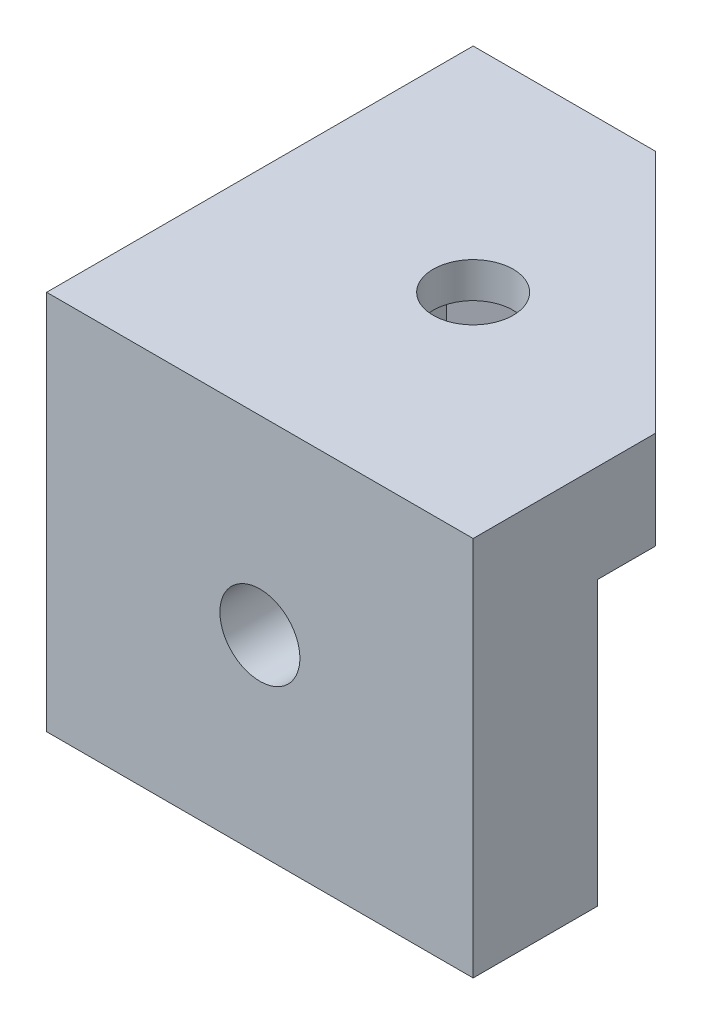
SolidWorks part; units mm, degrees
ref_plane "Front Plane" through (0, 0, 0) normal (0, 0, 1) x (1, 0, 0)
ref_plane "Top Plane" through (0, 0, 0) normal (0, 1, 0) x (1, 0, 0)
ref_plane "Right Plane" through (0, 0, 0) normal (1, 0, 0) x (0, 0, -1)
sketch "Sketch1" plane through (0, 0, 0) normal (0, 1, 0) x (1, 0, 0)
  line L1 (0, 0) -> (38.1, 0)
  line L5 (0, 0) -> (0, 38.1)
  line L6 (0, 38.1) -> (38.1, 38.1)
  line L8 (38.1, 38.1) -> (38.1, 0)
  dimension "D1" = 38.1
extrude "Main Body" add sketch "Sketch1" along normal blind 34
sketch "Sketch3" plane through (0, 0, 0) normal (0, 0, 1) x (1, 0, 0)
  line L0 (0, 0) -> (38.1, 34) construction
  circle A0 centre (19.05, 17) radius 3.5719
  circle A1 centre (19.05, 17) radius 7.9375 construction
  dimension "D1" = 7.1437
  dimension "D2" = 15.875
extrude "9/32 Right Rail" cut sketch "Sketch3" against normal blind 5.5562 and the other way through all
sketch "Sketch4" plane through (0, 0, 0) normal (-1, 0, 0) x (0, 0, 1)
  line L0 (0, 0) -> (-38.1, 34) construction
  circle A0 centre (-19.05, 17) radius 3.5719
  circle A1 centre (-19.05, 17) radius 7.9375 construction
  dimension "D1" = 7.1437
  dimension "D2" = 15.875
extrude "9/32 Left Rail" cut sketch "Sketch4" against normal blind 5.5562
sketch "Sketch8" plane through (0, 34, 0) normal (0, 1, 0) x (1, 0, 0)
  line L0 (0, 0) -> (38.1, 38.1) construction
  circle A0 centre (19.05, 19.05) radius 3.175 construction
  circle A1 centre (19.05, 19.05) radius 7.9375 construction
  circle A2 centre (19.05, 19.05) radius 3.5719
  dimension "D1" = 6.35
  dimension "D2" = 15.875
  dimension "D3" = 0.3969
extrude "9/32 Topper" cut sketch "Sketch8" against normal blind 10 and the other way through all
ref_plane "Plane1" through (5.5562, 0, 0) normal (-1, 0, 0) x (0, 0, 1)
sketch "Sketch9" plane through (0, 0, 0) normal (-1, 0, 0) x (0, 0, 1)
  line L0 (-19.05, 0) -> (-19.05, 34) construction
  line L1 (-12.6342, 17) -> (-15.8421, 22.5562) construction
  line L2 (-15.8421, 22.5562) -> (-22.2579, 22.5562) construction
  line L3 (-22.2579, 22.5562) -> (-25.4658, 17) construction
  line L4 (-25.4658, 17) -> (-22.2579, 11.4437) construction
  line L5 (-22.2579, 11.4437) -> (-15.8421, 11.4437) construction
  line L6 (-15.8421, 11.4437) -> (-12.6342, 17) construction
  line L7 (-38.1, 0) -> (0, 0) construction
  line L8 (-38.1, 34) -> (0, 34) construction
  line L9 (-22.3152, 22.6555) -> (-25.5804, 17)
  line L10 (-25.5804, 17) -> (-22.3152, 11.3445)
  line L11 (-22.3152, 11.3445) -> (-15.7848, 11.3445)
  line L12 (-15.7848, 11.3445) -> (-12.5196, 17)
  line L13 (-12.5196, 17) -> (-15.7848, 22.6555)
  line L14 (-15.7848, 22.6555) -> (-22.3152, 22.6555)
  line L15 (-38.1, 27.65) -> (-38.1, 6.35) construction
  line L16 (-38.1, 34) -> (-38.1, 0) construction
  line L17 (-38.1, 6.35) -> (-5.5562, 6.35) construction
  line L18 (-5.5562, 6.35) -> (-5.5562, 27.65) construction
  line L19 (-5.5562, 27.65) -> (-38.1, 27.65) construction
  line L20 (0, 34) -> (0, 0) construction
  circle A0 centre (-19.05, 17) radius 5.5563 construction
  point P15 (-19.05, 17)
  point P27 (-38.1, 17)
  point P29 (-38.1, 17)
  dimension "D1" = 11.1125
  dimension "D3" = 5.5562
  dimension "D4" = 6.35
  dimension "D2" = 0.0992
extrude "Hex Hole Right" cut sketch "Sketch9" against normal up to surface (38.1 mm away) from surface up to face at (38.1, 17, -19.05) starting at plane "Plane1"
ref_plane "Plane2" through (0, 0, -5.5563) normal (0, 0, 1) x (1, 0, 0)
sketch "Sketch10" plane through (0, 0, 0) normal (0, 0, 1) x (1, 0, 0)
  line L0 (19.05, 0) -> (19.05, 34) construction
  line L1 (0, 0) -> (38.1, 0) construction
  line L2 (0, 34) -> (38.1, 34) construction
  line L3 (15.7848, 22.6555) -> (12.5196, 17)
  line L4 (25.4658, 17) -> (22.2579, 22.5562) construction
  line L5 (22.2579, 22.5562) -> (15.8421, 22.5562) construction
  line L6 (15.8421, 22.5562) -> (12.6342, 17) construction
  line L13 (12.6342, 17) -> (15.8421, 11.4437) construction
  line L14 (15.8421, 11.4437) -> (22.2579, 11.4437) construction
  line L15 (22.2579, 11.4437) -> (25.4658, 17) construction
  line L16 (12.5196, 17) -> (15.7848, 11.3445)
  line L17 (15.7848, 11.3445) -> (22.3152, 11.3445)
  line L18 (22.3152, 11.3445) -> (25.5804, 17)
  line L19 (25.5804, 17) -> (22.3152, 22.6555)
  line L20 (22.3152, 22.6555) -> (15.7848, 22.6555)
  circle A0 centre (19.05, 17) radius 5.5563 construction
  dimension "D1" = 11.1125
  dimension "D2" = 0.0992
extrude "Hex Hole Left" cut sketch "Sketch10" against normal up to surface (38.1 mm away) from surface up to face at (19.05, 17, -38.1) starting at plane "Plane2"
sketch "Sketch13" plane through (0, 34, 0) normal (0, 1, 0) x (1, 0, 0)
  line L0 (22.3152, 5.5563) -> (15.7848, 5.5563) construction
  line L1 (5.5562, 15.7848) -> (5.5562, 22.3152) construction
  line L2 (38.1, 11.1125) -> (11.1125, 11.1125)
  line L3 (11.1125, 38.1) -> (11.1125, 11.1125)
  line L5 (22.3152, 5.5563) -> (15.7848, 5.5563) construction
  line L6 (5.5562, 15.7848) -> (5.5562, 22.3152) construction
  line L7 (38.1, 38.1) -> (0, 38.1) construction
  line L8 (38.1, 0) -> (38.1, 38.1) construction
  line L9 (11.1125, 38.1) -> (38.1, 38.1)
  line L10 (38.1, 38.1) -> (38.1, 11.1125)
  dimension "D1" = 5.5562
ref_plane "Plane4" through (0, 17, 0) normal (0, 1, 0) x (1, 0, 0)
extrude "Inner Cavity" cut sketch "Sketch13" along direction (0, -1, 0) on the side of the normal offset from surface 8.7312 and the other way up to surface (34 mm away) from surface up to face at (19.05, 34, -22.6219) other way up to face at (19.05, 0, -19.05) starting at plane "Plane4"
sketch "Sketch14" plane through (0, 34, 0) normal (0, 1, 0) x (1, 0, 0)
  line L0 (38.1, 0) -> (0, 38.1) construction
  line L1 (24.7055, 22.3152) -> (19.05, 25.5804)
  line L2 (24.6063, 22.2579) -> (19.05, 25.4658) construction
  line L3 (19.05, 25.4658) -> (13.4938, 22.2579) construction
  line L4 (13.4938, 22.2579) -> (13.4938, 15.8421) construction
  line L5 (13.4938, 15.8421) -> (19.05, 12.6342) construction
  line L6 (19.05, 12.6342) -> (24.6063, 15.8421) construction
  line L7 (24.6063, 15.8421) -> (24.6063, 22.2579) construction
  line L8 (19.05, 25.5804) -> (13.3945, 22.3152)
  line L9 (13.3945, 22.3152) -> (13.3945, 15.7848)
  line L10 (13.3945, 15.7848) -> (19.05, 12.5196)
  line L11 (19.05, 12.5196) -> (24.7055, 15.7848)
  line L12 (24.7055, 15.7848) -> (24.7055, 22.3152)
  line L14 (38.1, 38.1) -> (38.1, 11.1125) construction
  circle A0 centre (19.05, 19.05) radius 5.5562 construction
  dimension "D1" = 11.1125
  dimension "D2" = 0.0992
extrude "Hex Hole Top" cut sketch "Sketch14" along normal offset from surface (13.825 mm away) 3.175 from surface up to face at (19.05, 34, -22.6219) starting at plane "Plane4"
sketch "Sketch16" plane through (0, 34, 0) normal (0, 1, 0) x (1, 0, 0)
  line L0 (38.1, 38.1) -> (16.2767, 38.1)
  line L1 (38.1, 38.1) -> (0, 38.1) construction
  line L2 (16.2767, 38.1) -> (38.1, 16.2767)
  line L3 (38.1, 16.2767) -> (38.1, 38.1)
  line L4 (38.1, 0) -> (38.1, 38.1) construction
  circle A2 centre (19.05, 19.05) radius 3.5719 construction
  dimension "D1" = 7.9375
extrude "Top Corner" cut sketch "Sketch16" against normal up to next
sketch "Sketch17" plane through (0, 0, 0) normal (0, -1, 0) x (1, 0, 0)
  line L0 (38.1, -5.5563) -> (0, -5.5563) construction
  line L1 (38.1, 0) -> (38.1, -11.1125) construction
  line L2 (0, -38.1) -> (0, 0) construction
  line L3 (11.1125, -38.1) -> (0, -38.1) construction
  line L4 (5.5563, -38.1) -> (5.5563, 0) construction
  line L5 (0, 0) -> (38.1, 0) construction
  line L6 (6.35, -19.8438) -> (6.35, -18.2563) construction
  line L7 (19.8437, -4.7625) -> (18.2562, -4.7625)
  line L8 (19.8437, -4.7625) -> (19.8437, -6.35)
  line L9 (19.8437, -6.35) -> (18.2562, -6.35)
  line L10 (18.2562, -4.7625) -> (18.2562, -6.35)
  line L11 (19.8437, -4.7625) -> (18.2562, -6.35) construction
  line L12 (19.8437, -6.35) -> (18.2562, -4.7625) construction
  line L13 (6.35, -16.6687) -> (4.7625, -16.6687)
  line L14 (6.35, -16.6687) -> (6.35, -18.2563)
  line L15 (6.35, -18.2563) -> (4.7625, -18.2563)
  line L16 (4.7625, -16.6687) -> (4.7625, -18.2563)
  line L17 (6.35, -16.6687) -> (4.7625, -18.2563) construction
  line L18 (6.35, -18.2563) -> (4.7625, -16.6687) construction
  line L19 (6.35, -19.8438) -> (4.7625, -19.8438)
  line L20 (6.35, -19.8438) -> (6.35, -21.4313)
  line L21 (6.35, -21.4313) -> (4.7625, -21.4313)
  line L22 (4.7625, -19.8438) -> (4.7625, -21.4313)
  line L23 (6.35, -19.8438) -> (4.7625, -21.4313) construction
  line L24 (6.35, -21.4313) -> (4.7625, -19.8438) construction
  point P12 (19.05, -5.5563)
  point P17 (5.5563, -17.4625)
  point P22 (5.5563, -20.6375)
  point P27 (19.05, -5.5563)
  point P28 (5.5563, -19.05)
  point P29 (6.35, -19.05)
  dimension "D1" = 1.5875
  dimension "D2" = 1.5875
extrude "Cut-Extrude1" cut sketch "Sketch17" against normal blind 0.3969
